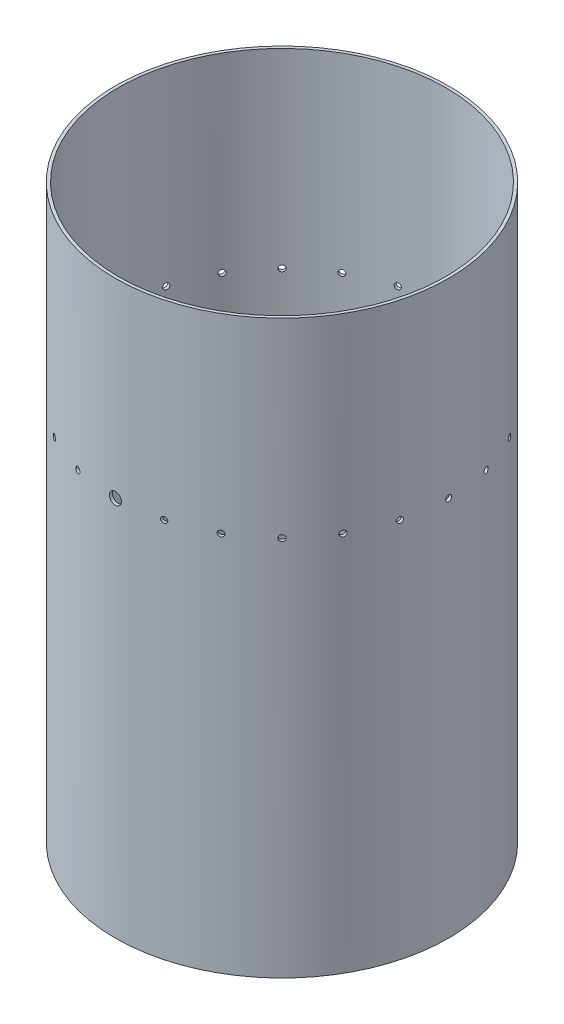
SolidWorks part; units mm, degrees
ref_plane "Front Plane" through (0, 0, 0) normal (0, 0, 1) x (1, 0, 0)
ref_plane "Top Plane" through (0, 0, 0) normal (0, 1, 0) x (1, 0, 0)
ref_plane "Right Plane" through (0, 0, 0) normal (1, 0, 0) x (0, 0, -1)
sketch "Sketch1" plane through (0, 0, 0) normal (0, 1, 0) x (1, 0, 0)
  circle A0 centre (0, 0) radius 88.9
  circle A1 centre (0, 0) radius 87.3125
  dimension "D1" = 177.8
  dimension "D2" = 174.625
extrude "Boss-Extrude1" add sketch "Sketch1" along normal blind 304.8
ref_plane "Plane1" through (0, 0, 88.9) normal (0, 0, 1) x (1, 0, 0)
sketch "Sketch10" plane through (0, 0, 88.9) normal (0, 0, 1) x (1, 0, 0)
  line L0 (88.9, 304.8) -> (-88.9, 304.8) construction
  circle A0 centre (0, 203.2) radius 1.5875
  dimension "D1" = 3.175
  dimension "D2" = 101.6
extrude "Cut-Extrude1" cut sketch "Sketch10" against normal blind 3.81
ref_axis "Axis1" through (0, 304.8, 0) along (0, -1, 0)
pattern_circular "CirPattern1" count 24 over 360 about axis through (0, 304.8, 0) along (0, -1, 0) of "Cut-Extrude1"
sketch "Sketch12" plane through (0, 0, 88.9) normal (0, 0, 1) x (1, 0, 0)
  circle A0 centre (0, 203.2) radius 3.175
  dimension "D1" = 6.35
extrude "Cut-Extrude2" cut sketch "Sketch12" against normal through all both and the other way through all
ref_axis "Axis2" through (0, 203.2, 87.0756) along (0, 0, 1)
